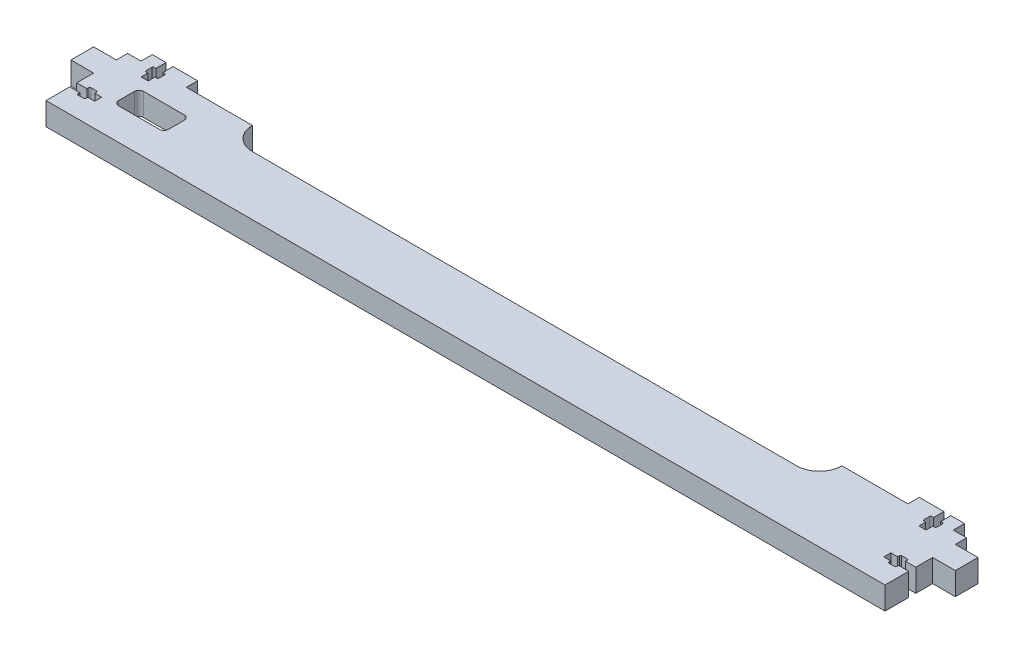
SolidWorks part; units mm, degrees
ref_plane "Front Plane" through (0, 0, 0) normal (0, 0, 1) x (1, 0, 0)
ref_plane "Top Plane" through (0, 0, 0) normal (0, 1, 0) x (1, 0, 0)
ref_plane "Right Plane" through (0, 0, 0) normal (1, 0, 0) x (0, 0, -1)
sketch "Sketch1" plane through (0, 0, 0) normal (0, 1, 0) x (1, 0, 0)
  line L0 (0, 18) -> (0, -18) construction
  line L1 (-185, 18) -> (0, 18)
  line L2 (-185, 18) -> (-185, 13)
  line L3 (-185, -18) -> (0, -18)
  line L4 (0, 18) -> (0, -18)
  line L5 (-185, 18) -> (0, 0) construction
  line L6 (-185, -18) -> (0, 0) construction
  line L7 (-185, 13) -> (-195, 13)
  line L8 (-195, 13) -> (-195, 3)
  line L9 (-195, 3) -> (-185, 3)
  line L10 (-185, 3) -> (-185, -18)
  point P0 (0, 0)
  dimension "D6" = 10
  dimension "D7" = 10
  dimension "D1" = 185
  dimension "D2" = 36
  dimension "D4" = 5
  dimension "D9" = 18
extrude "MainShape" add sketch "Sketch1" along normal blind 10 contours L2 L7 L8 L9 region at (-93.9423, 0, -0.1183)
sketch "Sketch15" plane through (0, 10, 0) normal (0, 1, 0) x (1, 0, 0)
  line L0 (-185, 18) -> (0, 18) construction
  line L1 (-159.1, 23) -> (-179.1, 23)
  line L2 (-159.1, 23) -> (-159.1, 13)
  line L3 (-159.1, 13) -> (-179.1, 13)
  line L4 (-179.1, 23) -> (-179.1, 13)
  line L5 (-159.1, 23) -> (-179.1, 13) construction
  line L6 (-159.1, 13) -> (-179.1, 23) construction
  line L7 (-185, 18) -> (-185, 13) construction
  point P0 (-169.1, 18)
  dimension "D1" = 20
  dimension "D2" = 5
  dimension "D3" = 15.9
extrude "Boss-Extrude4" add sketch "Sketch15" against normal through all
sketch "Sketch2" plane through (0, 10, 0) normal (0, 1, 0) x (1, 0, 0)
  line L0 (-171.5, 23) -> (-171.5, 12) construction
  line L2 (-173.05, 23) -> (-173.05, 18.5)
  line L3 (-173.05, 18.5) -> (-173.85, 18.5)
  line L4 (-174.35, 18) -> (-174.35, 15.5)
  line L5 (-173.85, 15) -> (-173.05, 15)
  line L6 (-173.05, 15) -> (-173.05, 12)
  line L7 (-173.05, 12) -> (-169.95, 12)
  line L8 (-185, 18) -> (-185, 13) construction
  line L9 (-173.05, 23) -> (-169.95, 23)
  line L10 (-169.95, 15) -> (-169.95, 12)
  line L11 (-169.15, 15) -> (-169.95, 15)
  line L12 (-168.65, 18) -> (-168.65, 15.5)
  line L13 (-169.95, 18.5) -> (-169.15, 18.5)
  line L14 (-169.95, 23) -> (-169.95, 18.5)
  line L16 (-185, -6) -> (-174, -6) construction
  line L17 (-159.1, 23) -> (-179.1, 23) construction
  line L50 (-185, 3) -> (-185, -18) construction
  line L51 (-174, -7.55) -> (-174, -4.45)
  line L52 (-174, -4.45) -> (-177, -4.45)
  line L53 (-177, -4.45) -> (-177, -3.65)
  line L54 (-177.5, -3.15) -> (-180, -3.15)
  line L55 (-180.5, -3.65) -> (-180.5, -4.45)
  line L56 (-180.5, -4.45) -> (-185, -4.45)
  line L57 (-185, -4.45) -> (-185, -7.55)
  line L58 (-195, 13) -> (-195, 3) construction
  line L59 (-180.5, -7.55) -> (-185, -7.55)
  line L60 (-180.5, -8.35) -> (-180.5, -7.55)
  line L61 (-177.5, -8.85) -> (-180, -8.85)
  line L62 (-177, -7.55) -> (-177, -8.35)
  line L63 (-174, -7.55) -> (-177, -7.55)
  arc A0 (-174.35, 15.5) -> (-173.85, 15) centre (-173.85, 15.5) ccw
  arc A1 (-173.85, 18.5) -> (-174.35, 18) centre (-173.85, 18) ccw
  arc A2 (-169.15, 18.5) -> (-168.65, 18) centre (-169.15, 18) cw
  arc A3 (-168.65, 15.5) -> (-169.15, 15) centre (-169.15, 15.5) cw
  arc A16 (-177, -3.65) -> (-177.5, -3.15) centre (-177.5, -3.65) ccw
  arc A17 (-180, -3.15) -> (-180.5, -3.65) centre (-180, -3.65) ccw
  arc A18 (-180, -8.85) -> (-180.5, -8.35) centre (-180, -8.35) cw
  arc A19 (-177, -8.35) -> (-177.5, -8.85) centre (-177.5, -8.35) cw
  point P14 (-174.35, 15)
  point P17 (-174.35, 18.5)
  point P28 (-168.65, 18.5)
  point P29 (-168.65, 15)
  point P34 (-195, 8)
  point P45 (-177, -3.15)
  point P48 (-180.5, -3.15)
  dimension "D8" = 0.5
  dimension "D16" = 0.5
  dimension "D1" = 11
  dimension "D2" = 1.55
  dimension "D3" = 1.55
  dimension "D5" = 2.85
  dimension "D6" = 3.5
  dimension "D7" = 13.5
  dimension "D9" = 11
  dimension "D10" = 8
  dimension "D11" = 3.5
  dimension "D12" = 2.85
  dimension "D13" = 1.55
  dimension "D14" = 1.55
  dimension "D15" = 14
  dimension "D4" = 8
extrude "ScrewSlots" cut sketch "Sketch2" against normal through all
mirror "Mirror1" about plane through (0, 0, 0) normal (1, 0, 0) of "Boss-Extrude4", "ScrewSlots", "MainShape"
sketch "Sketch6" plane through (0, 10, 0) normal (0, 1, 0) x (1, 0, 0)
  line L0 (0, -18) -> (0, -48) construction
  line L2 (-185, -18) -> (185, -18) construction
  line L3 (90, -48) -> (-90, -48)
  line L4 (-90, -48) -> (-120, -18)
  line L5 (90, -48) -> (120, -18)
  line L6 (-120, -18) -> (120, -18)
  dimension "D1" = 135
  dimension "D2" = 30
  dimension "D3" = 90
extrude "Boss-Extrude1" [suppressed] add sketch "Sketch6" against normal through all
sketch "Sketch8" plane through (0, 10, 0) normal (0, 1, 0) x (1, 0, 0)
  line L0 (-71.5, 4.8833) -> (-77.5, 4.8833) construction
  line L1 (-77, -1.6167) -> (-72, -1.6167)
  line L2 (-78, -0.6167) -> (-78, 4.3833)
  line L3 (-77, 5.3833) -> (-72, 5.3833)
  line L4 (-71, -0.6167) -> (-71, 4.3833)
  line L5 (-78, -1.6167) -> (-71, 5.3833) construction
  line L6 (-78, 5.3833) -> (-71, -1.6167) construction
  line L7 (-71.5, -1.1167) -> (-71.5, 4.8833) construction
  circle A0 centre (-74.5, -34.7667) radius 6.5
  circle A1 centre (-74.5, -15.8167) radius 5.5
  arc A2 (-77, -1.6167) -> (-78, -0.6167) centre (-77, -0.6167) cw
  circle A3 centre (-74.5, -34.7667) radius 6 construction
  circle A4 centre (-74.5, -15.8167) radius 3.5 construction
  arc A5 (-72, -1.6167) -> (-71, -0.6167) centre (-72, -0.6167) ccw
  arc A6 (-72, 5.3833) -> (-71, 4.3833) centre (-72, 4.3833) cw
  arc A7 (-78, 4.3833) -> (-77, 5.3833) centre (-77, 4.3833) cw
  point P6 (-74.5, 1.8833)
  dimension "D1" = 0.5
  dimension "D2" = 2
  dimension "D3" = 0.5
  dimension "D5" = 1
  dimension "D4" = 0.5
extrude "Cut-Extrude2" [suppressed] cut sketch "Sketch8" against normal through all
sketch "Sketch7" plane through (0, 10, 0) normal (0, 1, 0) x (1, 0, 0)
  circle A0 centre (60.5, -43.0167) radius 1.45
  circle A1 centre (-84.5, -43.0167) radius 1.45
  circle A2 centre (-84.5, 6.4833) radius 1.45
  circle A3 centre (60.5, 6.4833) radius 1.45
  dimension "D1" = 2.9
  dimension "D2" = 2.9
  dimension "D3" = 2.9
  dimension "D4" = 2.9
extrude "Cut-Extrude1" [suppressed] cut sketch "Sketch7" against normal through all
sketch "Sketch9" plane through (0, 10, 0) normal (0, 1, 0) x (1, 0, 0)
  line L0 (0, 7.2333) -> (0, -32.7667) construction
  line L1 (48.5, 7.2333) -> (-48.5, 7.2333) construction
  line L2 (-48.5, -32.7667) -> (48.5, -32.7667) construction
  line L3 (-48.5, -12.7667) -> (48.5, -12.7667) construction
  line L4 (-48.5, 7.2333) -> (-48.5, -32.7667) construction
  line L5 (48.5, -32.7667) -> (48.5, 7.2333) construction
  line L7 (-49, -33.2667) -> (49, -33.2667)
  line L8 (-49, -33.2667) -> (-49, 7.7333)
  line L9 (-49, 7.7333) -> (49, 7.7333)
  line L10 (49, -33.2667) -> (49, 7.7333)
  line L11 (-49, -33.2667) -> (49, 7.7333) construction
  line L12 (-49, 7.7333) -> (49, -33.2667) construction
  point P12 (0, -12.7667)
  dimension "D1" = 0.5
  dimension "D2" = 0.5
extrude "Cut-Extrude3" [suppressed] cut sketch "Sketch9" against normal through all and the other way through all
sketch "Sketch10" plane through (0, 10, 0) normal (0, 1, 0) x (1, 0, 0)
  line L0 (20, -39.2667) -> (20, -40.7667) construction
  line L1 (40, -39.2667) -> (0, -39.2667) construction
  line L2 (0, -40.7667) -> (40, -40.7667) construction
  line L3 (0, -40.0167) -> (40, -40.0167) construction
  line L4 (0, -39.2667) -> (0, -40.7667) construction
  line L5 (40, -40.7667) -> (40, -39.2667) construction
  line L7 (-0.2, -40.9667) -> (40.2, -40.9667)
  line L8 (-0.2, -40.9667) -> (-0.2, -39.0667)
  line L9 (-0.2, -39.0667) -> (40.2, -39.0667)
  line L10 (40.2, -40.9667) -> (40.2, -39.0667)
  line L11 (-0.2, -40.9667) -> (40.2, -39.0667) construction
  line L12 (-0.2, -39.0667) -> (40.2, -40.9667) construction
  point P12 (20, -40.0167)
  dimension "D1" = 0.2
  dimension "D2" = 0.2
extrude "Cut-Extrude4" [suppressed] cut sketch "Sketch10" against normal through all
sketch "Sketch12" [suppressed] plane through (0, 0, 0) normal (0, -1, 0) x (-1, 0, 0)
  line L1 (81.4, -9.8167) -> (67.6, -9.8167)
  line L2 (81.4, -9.8167) -> (81.4, -21.8167)
  line L3 (81.4, -21.8167) -> (67.6, -21.8167)
  line L4 (67.6, -9.8167) -> (67.6, -21.8167)
  line L5 (81.4, -9.8167) -> (67.6, -21.8167) construction
  line L6 (81.4, -21.8167) -> (67.6, -9.8167) construction
  point P0 (74.5, -15.8167)
  dimension "D1" = 13.8
  dimension "D2" = 12
extrude "PotentiometerAdjustment" [suppressed] cut sketch "Sketch12" against normal through all
sketch "Sketch11" plane through (0, 0, 0) normal (0, -1, 0) x (1, 0, 0)
  line L1 (-149, -7) -> (-167, -7)
  line L2 (-147, -5) -> (-147, 2)
  line L3 (-149, 4) -> (-167, 4)
  line L4 (-169, -5) -> (-169, 2)
  line L5 (-147, -7) -> (-169, 4) construction
  line L6 (-147, 4) -> (-169, -7) construction
  line L7 (173.05, -12) -> (169.95, -12) construction
  line L8 (-174, 7.55) -> (-174, 4.45) construction
  arc A0 (-147, 2) -> (-149, 4) centre (-149, 2) ccw
  arc A1 (-167, 4) -> (-169, 2) centre (-167, 2) ccw
  arc A2 (-167, -7) -> (-169, -5) centre (-167, -5) cw
  arc A3 (-149, -7) -> (-147, -5) centre (-149, -5) ccw
  point P0 (-158, -1.5)
  dimension "D3" = 2
  dimension "D1" = 22
  dimension "D2" = 11
  dimension "D4" = 5
  dimension "D5" = 5
extrude "LCDCableCutout" cut sketch "Sketch11" against normal through all
sketch "Sketch13" plane through (0, 10, 0) normal (0, 1, 0) x (1, 0, 0)
  line L0 (0, 18) -> (0, -18) construction
  line L1 (-169.95, 18) -> (169.95, 18) construction
  line L2 (-185, -18) -> (185, -18) construction
  line L3 (120, 18) -> (-120, 18) construction
  line L4 (120, 8) -> (-120, 8)
  line L5 (120, 28) -> (-120, 28)
  arc A0 (120, 8) -> (120, 28) centre (120, 18) ccw
  arc A1 (-120, 28) -> (-120, 8) centre (-120, 18) ccw
  point P8 (0, 18)
  dimension "D2" = 120
  dimension "D1" = 10
extrude "Cut-Extrude5" cut sketch "Sketch13" against normal through all
sketch "Sketch14" plane through (0, 10, 0) normal (0, 1, 0) x (1, 0, 0)
  line L1 (-169.95, 18) -> (169.95, 18) construction
  line L3 (-156.5, 18) -> (-156.5, 28) construction
  line L4 (-161.5, 18) -> (-151.5, 18)
  line L5 (-161.5, 18) -> (-161.5, 28)
  line L6 (-161.5, 28) -> (-151.5, 28)
  line L7 (-151.5, 18) -> (-151.5, 28)
  line L8 (-173.05, 12) -> (-169.95, 12) construction
  line L9 (154, 18) -> (154, 28) construction
  line L10 (149, 18) -> (149, 28)
  line L11 (159, 28) -> (149, 28)
  line L12 (159, 18) -> (159, 28)
  line L13 (159, 18) -> (149, 18)
  point P12 (-171.5, 12)
  dimension "D1" = 10
  dimension "D2" = 10
  dimension "D3" = 15
extrude "Boss-Extrude3" [suppressed] add sketch "Sketch14" against normal through all
equation "\"Y-ROD-SPACING\"=75"
equation "\"Y-BED-OFFSET\"=2"
equation "\"Y-BED-ROD-INSET\"=3.5"
equation "\"T-SLOT-NUT-FILLET-RADIUS\"=0.5"
equation "\"T-SLOT-SCREW-SHAFT-RADIUS\"=1.55"
equation "\"T-SLOT-SCREW-SHAFT-CUTOUT-LENGTH\"=11"
equation "\"T-SLOT-NUT-DEPTH\"=3.5"
equation "\"T-SLOT-NUT-WIDTH\"=2.85"
equation "\"T-SLOT-NUT-END-DISTANCE\"=8"
equation "\"ACRYLIC-TAB-CUTOUT-SIZE\"=\"ACRYLIC-THICKNESS\"+\"ACRYLIC-TAB-TOLERANCE\"*2"
equation "\"ACRYLIC-M3-HOLE\"=2.9"
equation "\"SMOOTHROD-CAP-SCREW-DISTANCE\"=20"
equation "\"D2@Sketch2\"=\"T-SLOT-SCREW-SHAFT-RADIUS\""
equation "\"D1@Sketch2\"=\"T-SLOT-SCREW-SHAFT-CUTOUT-LENGTH\""
equation "\"D6@Sketch2\"=\"T-SLOT-NUT-DEPTH\""
equation "\"D5@Sketch2\"=\"T-SLOT-NUT-WIDTH\""
equation "\"D3@Sketch2\"=\"T-SLOT-SCREW-SHAFT-RADIUS\""
equation "\"D8@Sketch2\"=\"T-SLOT-NUT-FILLET-RADIUS\""
equation "\"D4@Sketch2\"=\"T-SLOT-NUT-END-DISTANCE\""
equation "\"D11@Sketch2\"=\"T-SLOT-NUT-DEPTH\""
equation "\"D10@Sketch2\"=\"T-SLOT-NUT-END-DISTANCE\""
equation "\"D13@Sketch2\"=\"T-SLOT-SCREW-SHAFT-RADIUS\""
equation "\"D14@Sketch2\"=\"T-SLOT-SCREW-SHAFT-RADIUS\""
equation "\"D16@Sketch2\"=\"T-SLOT-NUT-FILLET-RADIUS\""
equation "\"D9@Sketch2\"=\"T-SLOT-SCREW-SHAFT-CUTOUT-LENGTH\""
equation "\"ACRYLIC-TAB-WIDTH\"=\"ACRYLIC-THICKNESS\""
equation "\"D6@Sketch1\"=\"ACRYLIC-TAB-WIDTH\""
equation "\"D7@Sketch1\"=\"ACRYLIC-TAB-WIDTH\""
equation "\"FRAME-WIDTH-INNER\"=370"
equation "\"D1@Sketch1\"=\"FRAME-WIDTH-INNER\"/2"
equation "\"X-ROD-SPACING\"=45"
equation "\"Z-ROD-SPACING\"=17.5"
equation "\"ACRYLIC-THICKNESS\"=10"
equation "\"ACRYLIC-THICKNESS2\"=4.5"
equation "\"NEMA17-HOLE-SPACING\"=31"
equation "\"NEMA17-CENTRAL-CUTOUT\"=22.5"
equation "\"Z-BRACKET-REACH\"=57"
equation "\"TOP-BRACKET-SPACING\"=40"
equation "\"SMOOTHROD-X-LENGTH\"=350"
equation "\"SMOOTHROD-Y-LENGTH\"=350"
equation "\"SMOOTHROD-Z-LENGTH\"=350"
equation "\"SMOOTHROD-TIGHTENING-HEADROOM\"=.25"
equation "\"LEADSCREW-Z-LENGTH\"=300"
equation "\"SCREW-LENGTH-FRAME\"=\"ACRYLIC-THICKNESS\" + 10"
equation "\"SCREW-HEAD-RADIUS\"=6"
equation "\"PRINTED-X-SMOOTHROD-DIAMETER\"=8.8"
equation "\"PRINTED-X-SMOOTHROD-CUTOUT\"=10"
equation "\"PRINTED-X-BASE-HEIGHT\"=10"
equation "\"PRINTED-LM8UU-CUTOUT-SIZE\"=15.5"
equation "\"PRINTED-LM8UU-CUTOUT-LENGTH\"=24.5"
equation "\"PRINTED-X-IDLER-HEIGHT\"=16"
equation "\"PSU-MOUNTING-WIDTH\"=95"
equation "\"PSU-MOUNTING-HEIGHT\"=177"
equation "\"D1@MainShape\"=\"ACRYLIC-THICKNESS\""
equation "\"Y-BELT-TO-ROD-DISTANCE\"=20"
equation "\"SPOOL-HOLDER-ROD-SPACING\"=150"
equation "\"Z-ROD-INSET\"=13.5"
equation "\"D7@Sketch2\"=\"Z-ROD-INSET\""
equation "\"D1@Sketch7\"=\"ACRYLIC-M3-HOLE\""
equation "\"D2@Sketch7\"=\"ACRYLIC-M3-HOLE\""
equation "\"D3@Sketch7\"=\"ACRYLIC-M3-HOLE\""
equation "\"D4@Sketch7\"=\"ACRYLIC-M3-HOLE\""
equation "\"Y-BED-SCREW-SPACING\"=209"
equation "\"Y-BED-SCREW-CUTOUT-SLOT-HEIGHT\"=2.5"
equation "\"ACRYLIC-TAB-TOLERANCE\"=-.05"
equation "\"SCREW-LENGTH-MOTOR\"=\"ACRYLIC-THICKNESS\" + 5"
equation "\"SCREW-LENGTH-EXTRUDER\"=28"
equation "\"PRINTED-M3-HOLE\"=3.5"
equation "\"PRINTED-M3-NUT-AF\"=6.25"
equation "\"ACRYLIC-X-CARRIAGE-WIDTH\"=55"
equation "\"ACRYLIC-X-CARRIAGE-HEIGHT\"=75"
equation "\"ACRYLIC-X-CARRIAGE-LM8UU-CUTOUT-WIDTH\"=24.25"
equation "\"ACRYLIC-X-CARRIAGE-LM8UU-CUTOUT-HEIGHT\"=11.0"
equation "\"ACRYLIC-X-CARRIAGE-SCREW-SPACING-X\"=15"
equation "\"ACRYLIC-X-CARRIAGE-SCREW-SPACING-Y\"=33"
equation "\"ACRYLIC-X-CARRIAGE-CENTER-TAB-SPACING\"=14"
equation "\"ACRYLIC-X-CARRIAGE-EXTRUDER-OFFSET\"=26"
equation "\"ACRYLIC-X-CARRIAGE-EXTRUDER-ANGLE\"=90"
equation "\"ACRYLIC-X-CARRIAGE-EXTRUDER-SHELF-DEPTH\"=\"ACRYLIC-X-CARRIAGE-EXTRUDER-OFFSET\" + 28"
equation "\"ACRYLIC-X-CARRIAGE-EXTRUDER-BRACE-SPACING\"=23"
equation "\"ACRYLIC-X-CARRIAGE-EXTRUDER-BRACE-TAB-OFFSET\"=20"
equation "\"ACRYLIC-X-CARRIAGE-EXTRUDER-BRACE-HEIGHT\"=35"
equation "\"ACRYLIC-X-CARRIAGE-EXTRUDER-BRACE-SCREW-SPACING\"=22"
equation "\"ACRYLIC-X-CARRIAGE-DUAL-WIDTH-MULTIPLIER\"=1.65"
equation "\"ACRYLIC-X-CARRIAGE-DUAL-HOTEND-SPACING\"=42"
equation "\"ACRYLIC-X-CARRIAGE-DUAL-WIDTH\"=75"
equation "\"ACRYLIC-X-CARRIAGE-DUAL-HOTEND-SEPARATION\"=36"
equation "\"ACRYLIC-X-CARRIAGE-DUAL-MOUNT-PLATE-DEPTH\"=75"
equation "\"ACRYLIC-X-CARRIAGE-DUAL-MOUNT-BRACE-WIDTH\"=33"
equation "\"ACRYLIC-X-CARRIAGE-DUAL-MOUNT-SCREW-WIDTH\"=40"
equation "\"BLOWER-FAN-WIDTH\"=15"
equation "\"D1@Sketch14\"=\"ACRYLIC-TAB-WIDTH\""
equation "\"D2@Sketch14\"=\"ACRYLIC-THICKNESS\""
equation "\"D3@Sketch15\"=\"Z-ROD-INSET\"+2.4"
equation "\"D12@Sketch2\"=\"T-SLOT-NUT-WIDTH\""
